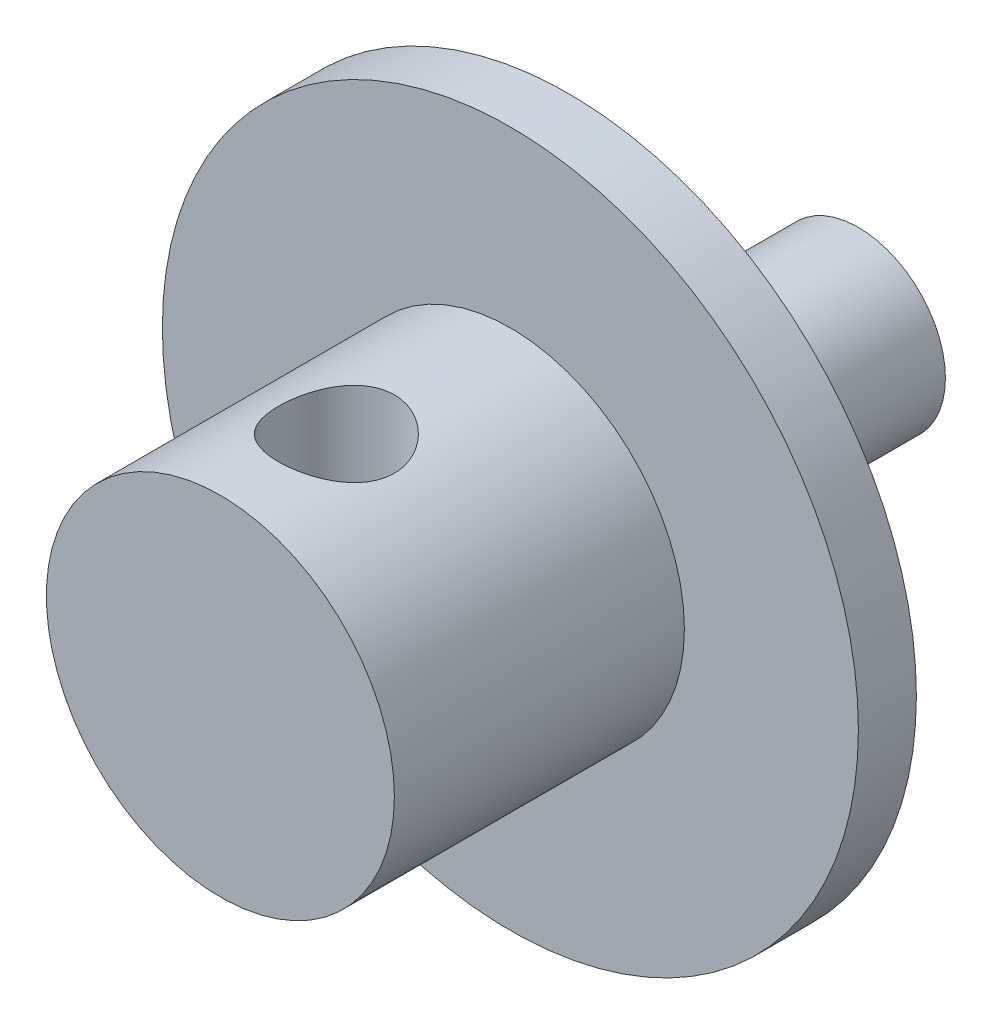
SolidWorks part; units mm, degrees
ref_plane "Plan de face" through (0, 0, 0) normal (0, 0, 1) x (1, 0, 0)
ref_plane "Plan de dessus" through (0, 0, 0) normal (0, 1, 0) x (1, 0, 0)
ref_plane "Plan de droite" through (0, 0, 0) normal (1, 0, 0) x (0, 0, -1)
sketch "Esquisse1" plane through (0, 0, 0) normal (0, 0, 1) x (1, 0, 0)
  circle A0 centre (0, 0) radius 1.5
  dimension "D1" = 3
extrude "Boss.-Extru.1" add sketch "Esquisse1" along normal blind 5
sketch "Esquisse2" plane through (0, 0, 5) normal (0, 0, 1) x (1, 0, 0)
  circle A0 centre (0, 0) radius 6
  dimension "D1" = 12
extrude "Boss.-Extru.2" add sketch "Esquisse2" along normal blind 1
sketch "Esquisse3" plane through (0, 0, 6) normal (0, 0, 1) x (1, 0, 0)
  circle A0 centre (0, 0) radius 3
  dimension "D1" = 6
extrude "Boss.-Extru.3" add sketch "Esquisse3" along normal blind 5
sketch "Esquisse4" plane through (0, 0, 0) normal (0, 1, 0) x (1, 0, 0)
  line L0 (0, 0) -> (0, -11) construction
  line L1 (-3, -11) -> (3, -11) construction
  circle A0 centre (0, -9) radius 1
  dimension "D1" = 2
  dimension "D2" = 2
extrude "Enlèv. mat.-Extru.1" cut sketch "Esquisse4" against normal blind 5 and the other way blind 5
